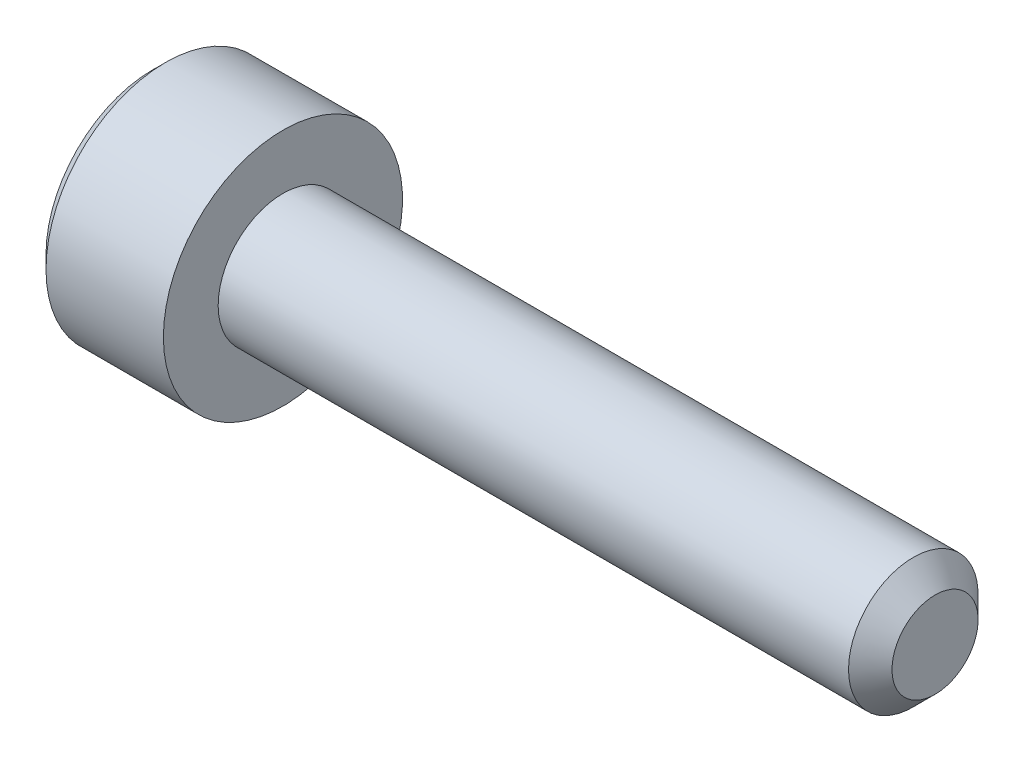
SolidWorks part; units mm, degrees
material "AISI Type 316L stainless steel"
ref_plane "Front Plane" through (0, 0, 0) normal (0, 0, 1) x (1, 0, 0)
ref_plane "Top Plane" through (0, 0, 0) normal (0, 1, 0) x (1, 0, 0)
ref_plane "Right Plane" through (0, 0, 0) normal (1, 0, 0) x (0, 0, -1)
sketch "Sketch1" plane through (0, 0, 0) normal (0, 0, 1) x (1, 0, 0)
  line L0 (-88.7055, 0) -> (96.9812, 0) construction
  line L1 (0, 0) -> (0, 2.75)
  line L2 (0, 2.75) -> (3, 2.75)
  line L4 (18, 0) -> (18, 1.49)
  line L5 (18, 1.49) -> (3, 1.49)
  line L6 (3, 1.49) -> (3, 2.75)
  line L7 (0, 0) -> (18, 0)
  dimension "D1" = 15
  dimension "D2" = 3
  dimension "D3" = 2.75
  dimension "D4" = 1.49
revolve "Revolve1" add sketch "Sketch1" angle 360 about L0
chamfer "Chamfer1" distance 0.5 angle 45 1 edges at (18, 0, 1.49)
chamfer "Chamfer2" distance 0.3 angle 45 1 edges at (0, 0, 2.75)
sketch "Sketch3" plane through (0, 0, 0) normal (1, 0, 0) x (0, 0, -1)
  line L1 (-1.4434, 0) -> (-0.7217, -1.25)
  line L2 (-0.7217, -1.25) -> (0.7217, -1.25)
  line L3 (0.7217, -1.25) -> (1.4434, 0)
  line L4 (1.4434, 0) -> (0.7217, 1.25)
  line L5 (0.7217, 1.25) -> (-0.7217, 1.25)
  line L6 (-0.7217, 1.25) -> (-1.4434, 0)
  circle A0 centre (0, 0) radius 1.25 construction
extrude "Cut-Extrude1" cut sketch "Sketch3" along normal blind 2.5
chamfer "Chamfer3" distance 0.3 angle 45 6 edges at (0, 1.25, 0) (0, 0.625, 1.0825) (0, -0.625, 1.0825) (0, -1.25, 0) (0, -0.625, -1.0825) (0, 0.625, -1.0825)
sketch "Sketch5" plane through (18, 0, 0) normal (1, 0, 0) x (0, 0, -1)
  circle A0 centre (0, 0) radius 1.49
curve "Helix/Spiral1" pitch 0.5 height 20 turns 40
sketch "Sketch8" plane through (0, 0, 0) normal (0, 1, 0) x (1, 0, 0)
  line L0 (18, 1.49) -> (18, 1.1111) construction
  line L1 (18.0625, 1.2194) -> (18.3281, 1.6794)
  line L2 (18.3281, 1.6794) -> (17.6719, 1.6794)
  line L3 (17.6719, 1.6794) -> (17.9375, 1.2194)
  line L4 (18, -0.99) -> (18, 0.99) construction
  circle A0 centre (18, 1.49) radius 0.1894 construction
  arc A1 (18.0625, 1.2194) -> (17.9375, 1.2194) centre (18, 1.2555) cw
  dimension "D2" = 0.0722
  dimension "D1" = 0.3789
sweep "Cut-Sweep1" [suppressed] cut profiles "Sketch8" path "Helix/Spiral1"
equation "\"length\"=15"
equation "\"D1@Sketch1\"=\"length\""
